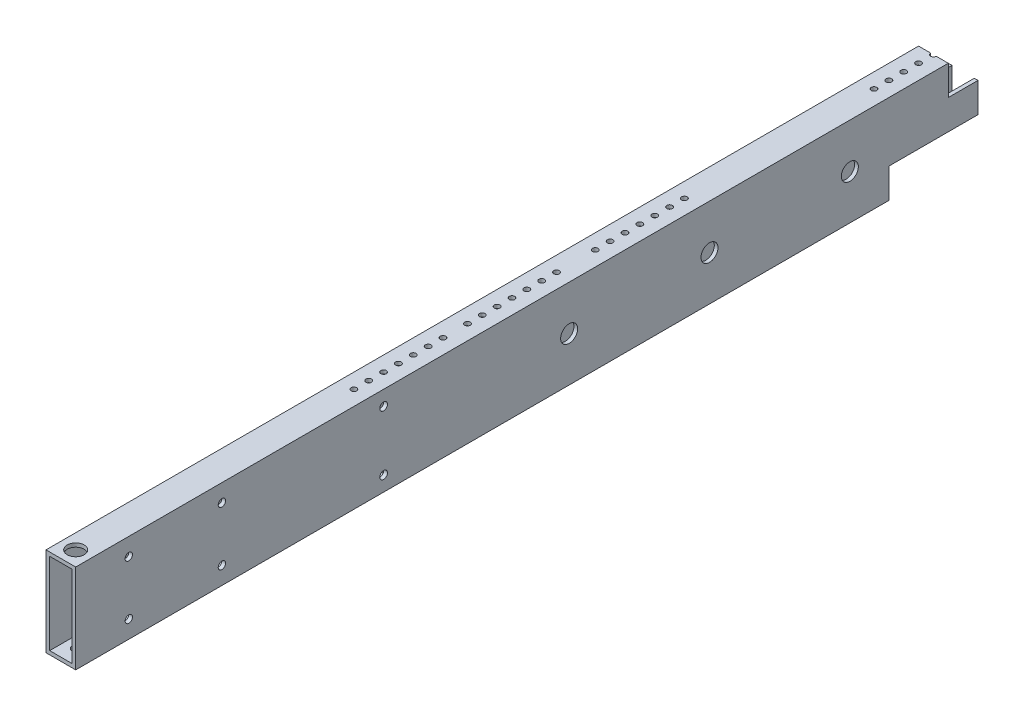
SolidWorks part; units mm, degrees
ref_plane "Front Plane" through (0, 0, 0) normal (0, 0, 1) x (1, 0, 0)
ref_plane "Top Plane" through (0, 0, 0) normal (0, 1, 0) x (1, 0, 0)
ref_plane "Right Plane" through (0, 0, 0) normal (1, 0, 0) x (0, 0, -1)
sketch "Sketch1" plane through (0, 0, 0) normal (0, 0, 1) x (1, 0, 0)
  line L1 (-12.7, -38.1) -> (12.7, -38.1)
  line L2 (-12.7, -38.1) -> (-12.7, 38.1)
  line L3 (-12.7, 38.1) -> (12.7, 38.1)
  line L4 (12.7, -38.1) -> (12.7, 38.1)
  line L5 (-12.7, -38.1) -> (12.7, 38.1) construction
  line L6 (-12.7, 38.1) -> (12.7, -38.1) construction
  point P0 (0, 0)
  dimension "D1" = 25.4
  dimension "D2" = 76.2
extrude "Boss-Extrude1" add sketch "Sketch1" along normal mid plane 771.398
shell "Shell1" thickness 3.175 removed face at (0, 0, -385.699) removed face at (0, 0, 385.699)
sketch "Sketch2" plane through (12.7, 0, 0) normal (1, 0, 0) x (0, 0, -1)
  line L1 (385.699, -38.1) -> (309.499, -38.1)
  line L2 (385.699, -38.1) -> (385.699, -12.7)
  line L3 (385.699, -12.7) -> (309.499, -12.7)
  line L4 (309.499, -38.1) -> (309.499, -12.7)
  dimension "D1" = 25.4
  dimension "D2" = 76.2
extrude "Cut-Extrude1" cut sketch "Sketch2" against normal through all
sketch "Sketch3" plane through (12.7, 0, 0) normal (1, 0, 0) x (0, 0, -1)
  line L1 (385.699, 38.1) -> (360.299, 38.1)
  line L2 (385.699, 38.1) -> (385.699, 12.7)
  line L3 (385.699, 12.7) -> (360.299, 12.7)
  line L4 (360.299, 38.1) -> (360.299, 12.7)
  dimension "D1" = 25.4
extrude "Cut-Extrude2" cut sketch "Sketch3" against normal through all
sketch "Sketch4" plane through (0, 38.1, 0) normal (0, 1, 0) x (1, 0, 0)
  line L0 (-12.7, 360.299) -> (12.7, 360.299) construction
  circle A0 centre (0, 147.3945) radius 2.3812
  circle A1 centre (0, 134.6945) radius 2.3812
  circle A2 centre (0, 121.9945) radius 2.3812
  circle A3 centre (0, 109.2945) radius 2.3812
  circle A4 centre (0, 96.5945) radius 2.3812
  circle A5 centre (0, 83.8945) radius 2.3812
  circle A6 centre (0, 71.1945) radius 2.3812
  circle A7 centre (0, 38.0987) radius 2.3812
  circle A8 centre (0, 25.3987) radius 2.3813
  circle A9 centre (0, 12.6987) radius 2.3813
  circle A10 centre (0, -0.0013) radius 2.3813
  circle A11 centre (0, -12.7013) radius 2.3812
  circle A12 centre (0, -25.4013) radius 2.3812
  circle A13 centre (0, -38.1013) radius 2.3812
  circle A15 centre (0, -58.9932) radius 2.3812
  circle A16 centre (0, -71.6932) radius 2.3812
  circle A17 centre (0, -84.3932) radius 2.3812
  circle A18 centre (0, -97.0932) radius 2.3812
  circle A19 centre (0, -109.7932) radius 2.3812
  circle A20 centre (0, -122.4932) radius 2.3812
  circle A21 centre (0, -135.1932) radius 2.3813
  point P33 (0, 360.299)
  dimension "D1" = 4.7625
  dimension "D3" = 12.7
  dimension "D4" = 12.7
  dimension "D5" = 12.7
  dimension "D6" = 12.7
  dimension "D7" = 12.7
  dimension "D8" = 12.7
  dimension "D9" = 322.2003
  dimension "D10" = 12.7
  dimension "D11" = 12.7
  dimension "D12" = 12.7
  dimension "D13" = 12.7
  dimension "D14" = 12.7
  dimension "D15" = 12.7
  dimension "D16" = 12.7
  dimension "D17" = 419.2922
  dimension "D18" = 12.7
  dimension "D19" = 12.7
  dimension "D20" = 12.7
  dimension "D21" = 12.7
  dimension "D22" = 12.7
  dimension "D2" = 212.9045
extrude "Cut-Extrude3" cut sketch "Sketch4" against normal through all
sketch "Sketch5" plane through (0, 38.1, 0) normal (0, 1, 0) x (1, 0, 0)
  line L0 (-12.7, 360.299) -> (12.7, 360.299) construction
  circle A0 centre (0, 360.299) radius 2.3813
  circle A1 centre (0, 347.599) radius 2.3813
  circle A2 centre (0, 334.899) radius 2.3813
  circle A3 centre (0, 322.199) radius 2.3813
  circle A4 centre (0, 309.499) radius 2.3813
  dimension "D1" = 4.7625
  dimension "D3" = 12.7
  dimension "D4" = 12.7
  dimension "D5" = 12.7
  dimension "D8" = 0
  dimension "D2" = 12.7
extrude "Cut-Extrude4" cut sketch "Sketch5" against normal up to next
sketch "Sketch6" plane through (0, -38.1, 0) normal (0, -1, 0) x (1, 0, 0)
  line L0 (-12.7, -309.499) -> (12.7, -309.499) construction
  circle A0 centre (0, -309.499) radius 2.3813
  circle A1 centre (0, -296.799) radius 2.3813
  circle A2 centre (0, -284.099) radius 2.3813
  circle A3 centre (0, -258.699) radius 2.3813
  circle A6 centre (0, -271.399) radius 2.3813
  dimension "D1" = 4.7625
  dimension "D2" = 12.7
  dimension "D3" = 12.7
  dimension "D4" = 12.7
  dimension "D5" = 12.7
  dimension "D6" = 0
extrude "Cut-Extrude5" cut sketch "Sketch6" against normal up to next
sketch3d "3DSketch1" [suppressed]
  line L0 (0, 34.925, -109.2945) -> (0, 38.1, -109.2945) construction
  line L1 (0, 34.925, 97.0932) -> (0, 38.1, 97.0932) construction
  point P0 (0, 38.1, -109.2945)
  point P1 (0, 0, 0)
  point P4 (0, 38.1, 97.0932)
sketch "Sketch11" plane through (12.7, 0, 0) normal (1, 0, 0) x (0, 0, -1)
  point P0 (-340.3244, 23.1254)
  point P1 (-260.7244, 23.1254)
  point P3 (-260.7244, -23.1)
  point P5 (-340.3244, -23.1)
hole_wizard "CBORE for M6 Hex Head Bolt1" positions "Sketch19" profile "Sketch18" counterbore size "M6" standard "Lanco STD" end condition through all
sketch "Sketch19" plane through (-12.7, 0, 0) normal (-1, 0, 0) x (0, 0, 1)
  point P0 (260.7244, 23.1254)
  point P3 (260.7244, -23.1)
  point P6 (340.3244, 23.1254)
  point P9 (340.3244, -23.1)
sketch "Sketch18" plane through (-12.7, 23.1254, 260.7244) normal (0, 1, 0) x (0, 0, 1)
  line L0 (0, 0) -> (0, 25.4)
  line L1 (0, 25.4) -> (3.15, 25.4)
  line L3 (3.15, 25.4) -> (3.15, 4)
  line L4 (3.15, 4) -> (7.2735, 4)
  line L5 (7.2735, 4) -> (7.2735, 0)
  line L7 (7.2735, 0) -> (0, 0)
  line L11 (0, -6.35) -> (0, 107.95) construction
  dimension "Thru Hole Dia." = 6.3
  dimension "Thru Hole Depth" = 25.4
  dimension "C'Bore Dia." = 14.547
  dimension "C'Bore Depth" = 4
hole_wizard "CBORE for M6 Hex Head Cap Screw1" positions "Sketch21" profile "Sketch20" counterbore size "M6" standard "ANSI Metric" end condition through all
sketch "Sketch21" plane through (-12.7, 0, 0) normal (-1, 0, 0) x (0, 0, 1)
  line L0 (385.699, 38.1) -> (-360.299, 38.1) construction
  line L1 (385.699, 38.1) -> (385.699, -38.1) construction
  point P0 (122.4678, 25.4)
  point P2 (122.4678, -25.4)
  dimension "D1" = 12.7
  dimension "D2" = 63.5
  dimension "D3" = 263.2312
  dimension "D4" = 263.2312
sketch "Sketch20" plane through (-12.7, 25.4, 122.4678) normal (0, 1, 0) x (0, 0, 1)
  line L0 (0, 0) -> (0, 25.4)
  line L1 (0, 25.4) -> (3.3, 25.4)
  line L3 (3.3, 25.4) -> (3.3, 4.15)
  line L4 (3.3, 4.15) -> (7.275, 4.15)
  line L5 (7.275, 4.15) -> (7.275, 0)
  line L7 (7.275, 0) -> (0, 0)
  line L11 (0, -6.35) -> (0, 107.95) construction
  dimension "Thru Hole Dia." = 6.6
  dimension "Thru Hole Depth" = 25.4
  dimension "C'Bore Dia." = 14.55
  dimension "C'Bore Depth" = 4.15
hole_wizard "CBORE for M6 Hex Head Cap Screw2" positions "Sketch26" profile "Sketch25" counterbore size "M6" standard "ANSI Metric" end condition through all
sketch "Sketch26" plane through (0, 38.1, 0) normal (0, 1, 0) x (1, 0, 0)
  line L0 (12.7, -385.699) -> (-12.7, -385.699) construction
  point P0 (0, -372.999)
  dimension "D1" = 12.7
sketch "Sketch25" plane through (0, 38.1, 372.999) normal (1, 0, 0) x (0, 0, 1)
  line L0 (0, 0) -> (0, 76.2)
  line L1 (0, 76.2) -> (3.3, 76.2)
  line L3 (3.3, 76.2) -> (3.3, 4.15)
  line L4 (3.3, 4.15) -> (7.275, 4.15)
  line L5 (7.275, 4.15) -> (7.275, 0)
  line L7 (7.275, 0) -> (0, 0)
  line L11 (0, -6.35) -> (0, 107.95) construction
  dimension "Thru Hole Dia." = 6.6
  dimension "Thru Hole Depth" = 76.2
  dimension "C'Bore Dia." = 14.55
  dimension "C'Bore Depth" = 4.15
hole_wizard "CBORE for M6 Hex Head Cap Screw3" positions "Sketch28" profile "Sketch27" counterbore size "M6" standard "ANSI Metric" end condition through all
sketch "Sketch28" plane through (12.7, 0, 0) normal (1, 0, 0) x (0, 0, -1)
  point P9 (36.1449, 0)
  point P13 (156.1449, 0)
  point P15 (276.1449, 0)
sketch "Sketch27" plane through (12.7, 0, -36.1449) normal (0, 1, 0) x (0, 0, -1)
  line L0 (0, 0) -> (0, 25.4)
  line L1 (0, 25.4) -> (3.3, 25.4)
  line L3 (3.3, 25.4) -> (3.3, 4.15)
  line L4 (3.3, 4.15) -> (7.275, 4.15)
  line L5 (7.275, 4.15) -> (7.275, 0)
  line L7 (7.275, 0) -> (0, 0)
  line L11 (0, -6.35) -> (0, 107.95) construction
  dimension "Thru Hole Dia." = 6.6
  dimension "Thru Hole Depth" = 25.4
  dimension "C'Bore Dia." = 14.55
  dimension "C'Bore Depth" = 4.15
